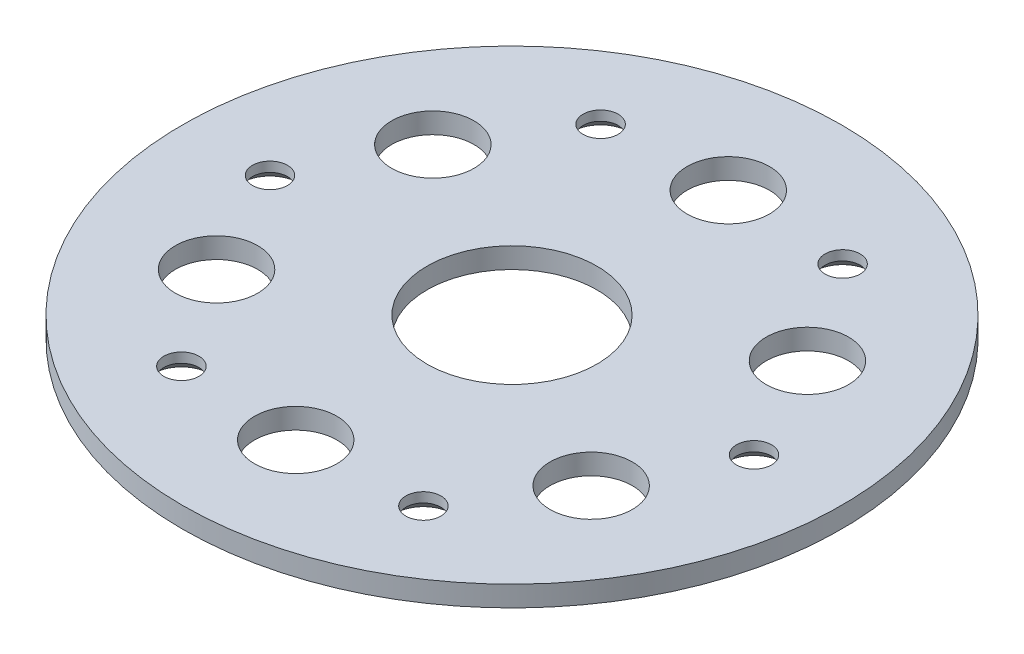
SolidWorks part; units mm, degrees
ref_plane "Front Plane" through (0, 0, 0) normal (0, 0, 1) x (1, 0, 0)
ref_plane "Top Plane" through (0, 0, 0) normal (0, 1, 0) x (1, 0, 0)
ref_plane "Right Plane" through (0, 0, 0) normal (1, 0, 0) x (0, 0, -1)
sketch "Sketch1" plane through (0, 0, 0) normal (0, 1, 0) x (1, 0, 0)
  circle A0 centre (0, 0) radius 8.25
  circle A1 centre (0, 0) radius 32
  dimension "D1" = 16.5
  dimension "D2" = 64
extrude "Boss-Extrude1" add sketch "Sketch1" along normal blind 2
sketch "Sketch2" plane through (0, 2, 0) normal (0, 1, 0) x (1, 0, 0)
  circle A0 centre (0, 21) radius 4
  circle A1 centre (0, 0) radius 21 construction
  circle A2 centre (18.1865, 10.5) radius 4
  circle A3 centre (18.1865, -10.5) radius 4
  circle A4 centre (0, -21) radius 4
  circle A5 centre (-18.1865, -10.5) radius 4
  circle A6 centre (-18.1865, 10.5) radius 4
  point P17 (0, 0)
  dimension "D1" = 8
  dimension "D2" = 42
  dimension "D3" = 6
extrude "Cut-Extrude1" cut sketch "Sketch2" against normal through all and the other way through all
hole_wizard "CSK for M3 Hex Socket Countersunk Head Screw1" positions "Sketch3" profile "Sketch4" countersink size "M3" standard "DIN" end condition up to next
sketch "Sketch3" plane through (0, 0, 0) normal (0, 1, 0) x (1, 0, 0)
  line L0 (0, 0) -> (18.891, 32.7202) construction
  circle A0 centre (0, 0) radius 23.5
  point P8 (11.75, 20.3516)
  point P14 (23.5, 0)
  point P15 (11.75, -20.3516)
  point P16 (-11.75, -20.3516)
  point P17 (-23.5, 0)
  point P18 (-11.75, 20.3516)
  dimension "D2" = 47
  dimension "D1" = 60
  dimension "D3" = 6
sketch "Sketch4" plane through (-11.75, 0, -20.3516) normal (1, 0, 0) x (0, 0, -1)
  line L0 (0, 0) -> (0, 2)
  line L1 (0, 2) -> (1.7, 2)
  line L2 (1.7, 2) -> (1.7, 1.05)
  line L3 (1.7, 1.05) -> (2.75, 0)
  line L5 (2.75, 0) -> (0, 0)
  line L6 (-1.7, 1.05) -> (-2.75, 0) construction
  line L11 (0, -6.35) -> (0, 107.95) construction
  dimension "Thru Hole Dia." = 3.4
  dimension "Thru Hole Depth" = 2
  dimension "Near C'Sink Dia." = 5.5
  dimension "Near C'Sink Angle" = 90
